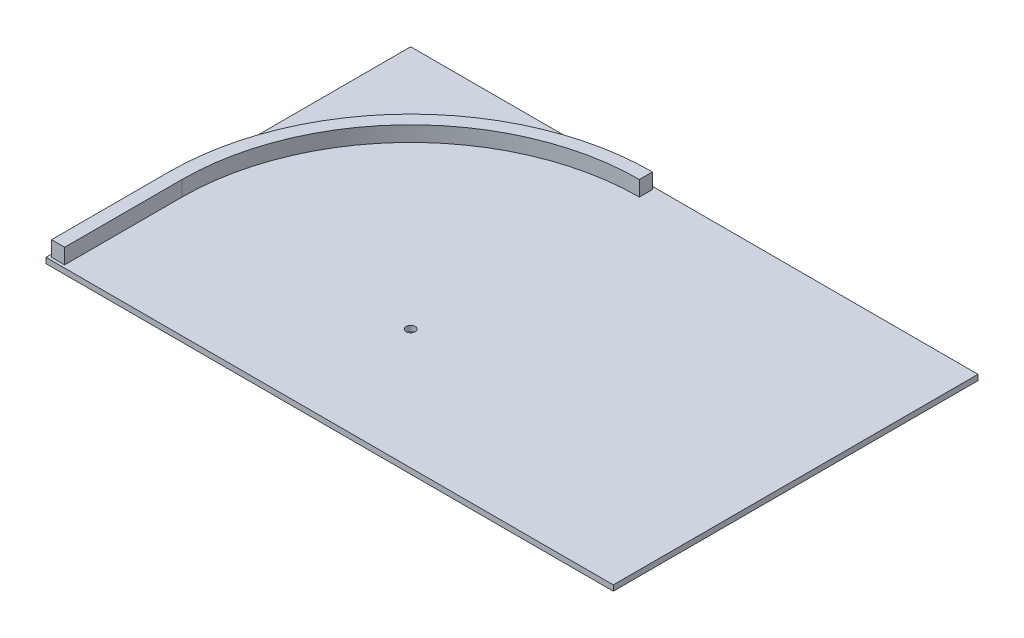
SolidWorks part; units mm, degrees
ref_plane "Front Plane" through (0, 0, 0) normal (0, 0, 1) x (1, 0, 0)
ref_plane "Top Plane" through (0, 0, 0) normal (0, 1, 0) x (1, 0, 0)
ref_plane "Right Plane" through (0, 0, 0) normal (1, 0, 0) x (0, 0, -1)
sketch "Sketch3" plane through (0, 0, 0) normal (0, 1, 0) x (1, 0, 0)
  line L0 (0, 524) -> (0, 554)
  line L1 (0, 0) -> (-839.8654, 0) construction
  line L2 (0, 0) -> (-451.1992, 260.5) construction
  line L5 (-524, 0) -> (-554, 0)
  circle A0 centre (0, 0) radius 254 construction
  arc A3 (0, 524) -> (-524, 0) centre (0, 0) ccw
  arc A4 (0, 554) -> (-554, 0) centre (0, 0) ccw
  dimension "D1" = 524
  dimension "D2" = 30
  dimension "D3" = 30
extrude "Boss-Extrude1" add sketch "Sketch3" along normal blind 35
sketch "Sketch4" plane through (0, 0, 0) normal (0, 1, 0) x (1, 0, 0)
  line L5 (-560.35, 560.35) -> (739.65, 560.35)
  line L6 (-560.35, 560.35) -> (-560.35, -275.4)
  line L7 (-560.35, -275.4) -> (739.65, -275.4)
  line L8 (739.65, 560.35) -> (739.65, -275.4)
  dimension "D1" = 275.4
  dimension "D2" = 6.35
  dimension "D3" = 6.35
  dimension "D4" = 1300
extrude "Boss-Extrude2" add sketch "Sketch4" against normal blind 12.7
hole_wizard "Ø20.0mm Dowel Hole1" positions "Sketch6" profile "Sketch7" hole size "Ø20.0" standard "ANSI Metric" end condition through all
sketch "Sketch6" plane through (0, 0, 0) normal (0, 1, 0) x (1, 0, 0)
  point P0 (0, 0)
sketch "Sketch7" plane through (0, 0, 0) normal (1, 0, 0) x (0, 0, 1)
  line L0 (0, 0) -> (0, 12.7)
  line L1 (0, 12.7) -> (10.5, 12.7)
  line L2 (10.5, 12.7) -> (10.5, 0)
  line L5 (10.5, 0) -> (0, 0)
  line L11 (0, -6.35) -> (0, 107.95) construction
  dimension "Thru Hole Dia." = 21
  dimension "Thru Hole Depth" = 12.7
ref_plane "Plane1" through (0, 0, 269.05) normal (0, 0, 1) x (1, 0, 0)
sketch "Sketch8" plane through (0, 0, 0) normal (0, 0, 1) x (1, 0, 0)
  line L1 (-554, 35) -> (-524, 35)
  line L2 (-554, 35) -> (-554, 0)
  line L3 (-554, 0) -> (-524, 0)
  line L4 (-524, 35) -> (-524, 0)
extrude "Boss-Extrude3" add sketch "Sketch8" along normal up to surface (269.05 mm away) up to plane "Plane1"
equation "\"D3@Sketch4\"=\"D2@Sketch4\""
